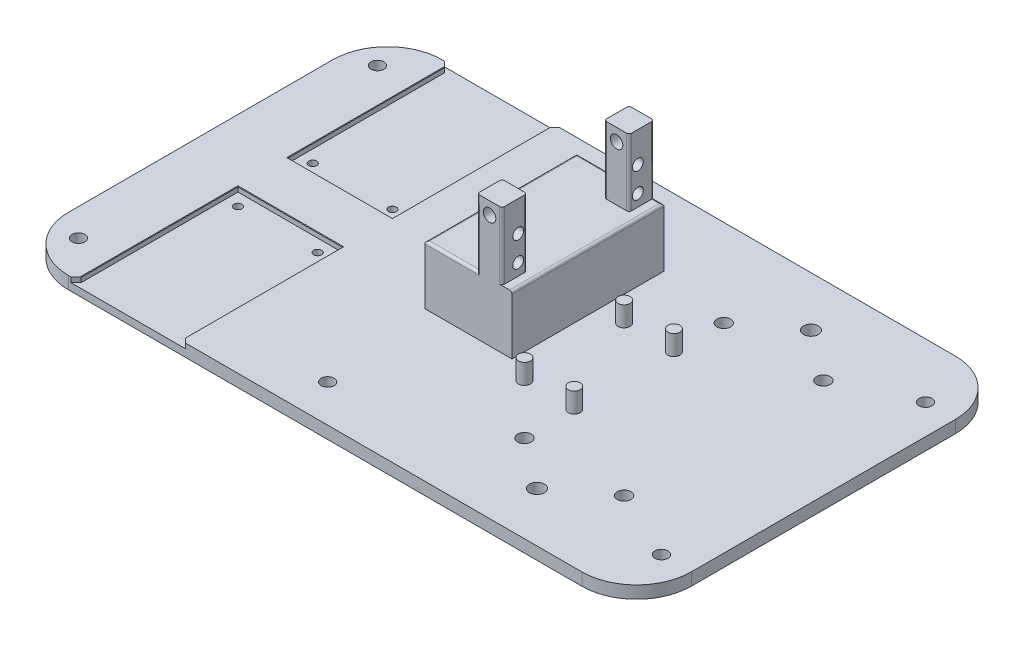
SolidWorks part; units mm, degrees
ref_plane "前视基准面" through (0, 0, 0) normal (0, 0, 1) x (1, 0, 0)
ref_plane "上视基准面" through (0, 0, 0) normal (0, 1, 0) x (1, 0, 0)
ref_plane "右视基准面" through (0, 0, 0) normal (1, 0, 0) x (0, 0, -1)
other "Configuration Table"
sketch "草图1" plane through (0, 0, 0) normal (0, 1, 0) x (1, 0, 0)
  line L0 (103, 75) -> (95, 75)
  line L5 (-125, 53) -> (-125, -53)
  line L6 (-103, -75) -> (55, -75)
  line L7 (125, -53) -> (125, 53)
  line L8 (-1000, 0) -> (49000, 0) construction
  line L9 (55, -75) -> (95, -75)
  line L14 (55, 75) -> (95, 75)
  line L15 (45, -40) -> (85, -40) construction
  line L20 (55, 75) -> (-103, 75)
  line L21 (95, -75) -> (103, -75)
  arc A0 (125, 53) -> (103, 75) centre (103, 53) ccw
  arc A1 (-103, 75) -> (-125, 53) centre (-103, 53) ccw
  arc A2 (-125, -53) -> (-103, -75) centre (-103, -53) ccw
  arc A3 (103, -75) -> (125, -53) centre (103, -53) ccw
  circle A4 centre (-114, 60) radius 2.6
  circle A5 centre (-14, 60) radius 2.6
  circle A6 centre (113, 53) radius 2.6
  circle A7 centre (-114, -60) radius 2.6
  circle A8 centre (-14, -60) radius 2.6
  circle A9 centre (113, -53) radius 2.6
  circle A10 centre (65, -55) radius 3
  circle A11 centre (65, 55) radius 3
  circle A12 centre (45, -40) radius 2.75
  circle A13 centre (85, -40) radius 2.75
  circle A14 centre (85, 40) radius 2.75
  circle A15 centre (45, 40) radius 2.75
  dimension "D3" = 22
  dimension "D4" = 22
  dimension "D5" = 22
  dimension "D6" = 22
  dimension "D9" = 100
  dimension "D10" = 127
  dimension "D11" = 22
  dimension "D12" = 127
  dimension "D13" = 100
  dimension "D14" = 120
  dimension "D15" = 7
  dimension "D16" = 11
  dimension "D17" = 60
  dimension "D18" = 20
  dimension "D19" = 6
  dimension "D20" = 5.5
  dimension "D21" = 5.5
  dimension "D23" = 20
  dimension "D24" = 20
  dimension "D25" = 5.2
  dimension "D1" = 150
  dimension "D2" = 250
  dimension "D7" = 125
  dimension "D8" = 75
  dimension "D22" = 15
extrude "凸台-拉伸1" add sketch "草图1" along normal blind 5
sketch "草图2" plane through (0, 5, 0) normal (0, 1, 0) x (1, 0, 0)
  line L0 (-103, -75) -> (103, -75) construction
  line L1 (-100, -75) -> (-58, -75)
  line L2 (-100, -75) -> (-100, -10)
  line L3 (-100, -10) -> (-58, -10)
  line L4 (-58, -75) -> (-58, -10)
  line L5 (-125, 53) -> (-125, -53) construction
  line L6 (-1000, 0) -> (49000, 0) construction
  line L7 (-58, 75) -> (-58, 10)
  line L8 (-100, 10) -> (-58, 10)
  line L9 (-100, 75) -> (-100, 10)
  line L10 (-100, 75) -> (-58, 75)
  dimension "D1" = 42
  dimension "D2" = 25
  dimension "D3" = 65
extrude "切除-拉伸1" cut sketch "草图2" against normal blind 2
chamfer "倒角1" distance 0.2 angle 45 6 edges at (-58, 5, -42.5) (-79, 5, -10) (-100, 5, -42.5) (-58, 5, 42.5) (-79, 5, 10) (-100, 5, 42.5)
sketch "草图3" plane through (0, 3, 0) normal (0, 1, 0) x (1, 0, 0)
  line L0 (-1000, 0) -> (49000, 0) construction
  line L1 (-100, 10) -> (-58, 10) construction
  line L2 (-58, 10) -> (-58, 75) construction
  line L3 (-100, 75) -> (-100, 10) construction
  circle A0 centre (-95, 15) radius 1.6
  circle A1 centre (-63, 15) radius 1.6
  circle A2 centre (-63, -15) radius 1.6
  circle A3 centre (-95, -15) radius 1.6
  dimension "D1" = 3.2
  dimension "D2" = 3.2
  dimension "D3" = 5
  dimension "D4" = 5
  dimension "D5" = 5
  dimension "D6" = 5
extrude "切除-拉伸2" cut sketch "草图3" against normal blind 3
sketch "草图4" plane through (0, 5, 0) normal (0, 1, 0) x (1, 0, 0)
  line L0 (-1000, 0) -> (49000, 0) construction
  line L1 (0, -1000) -> (0, 49000) construction
  line L2 (103, 75) -> (-57.8, 75) construction
  line L3 (25, -20) -> (45, -20) construction
  line L4 (25, -20) -> (25, 20) construction
  line L5 (25, 20) -> (45, 20) construction
  line L6 (45, -20) -> (45, 20) construction
  line L7 (25, -20) -> (45, 20) construction
  line L8 (25, 20) -> (45, -20) construction
  line L9 (-20, 46) -> (10, 46) construction
  line L10 (-20, 46) -> (-20, -15) construction
  line L11 (-20, -15) -> (10, -15) construction
  line L12 (10, 46) -> (10, -15) construction
  line L13 (-57.8, -75) -> (103, -75) construction
  line L14 (-125, 53) -> (-125, -53) construction
  circle A0 centre (25, 20) radius 2.4
  circle A1 centre (45, 20) radius 2.4
  circle A2 centre (45, -20) radius 2.4
  circle A3 centre (25, -20) radius 2.4
  point P4 (35, 0)
  dimension "D4" = 4.8
  dimension "D1" = 40
  dimension "D2" = 20
  dimension "D3" = 25
  dimension "D7" = 29
  dimension "D8" = 60
  dimension "D9" = 30
  dimension "D10" = 105
  dimension "D5" = 2
  dimension "D6" = 2
chamfer "倒角2" distance 2 4 edges at (-100, 3.9, -75) (-58, 3.9, -75) (-58, 3.9, 75) (-100, 3.9, 75)
extrude "凸台-拉伸2" add sketch "草图4" along normal blind 8
sketch "草图5" plane through (0, 5, 0) normal (0, 1, 0) x (1, 0, 0)
  line L0 (-56, -75) -> (103, -75) construction
  line L1 (-20, 46) -> (15, 46)
  line L2 (-20, 46) -> (-20, -15)
  line L3 (-20, -15) -> (15, -15)
  line L4 (15, 46) -> (15, -15)
  line L5 (103, 75) -> (-56, 75) construction
  line L6 (-125, 53) -> (-125, -53) construction
  dimension "D1" = 60
  dimension "D2" = 29
  dimension "D3" = 105
  dimension "D4" = 35
extrude "凸台-拉伸3" add sketch "草图5" along normal blind 23.5
sketch "草图7" plane through (0, 28.5, 0) normal (0, 1, 0) x (1, 0, 0)
  line L0 (15, -15) -> (15, 46) construction
  line L1 (-20, 46) -> (15, 46)
  line L2 (-20, 46) -> (-20, 36)
  line L3 (-20, 36) -> (15, 36)
  line L4 (15, 46) -> (15, 36)
  line L5 (-1020, 15.5) -> (48980, 15.5) construction
  line L6 (-20, 46) -> (-20, -15) construction
  line L7 (15, -15) -> (15, -5)
  line L8 (-20, -5) -> (15, -5)
  line L9 (-20, -15) -> (-20, -5)
  line L10 (-20, -15) -> (15, -15)
  point P12 (-20, 15.5)
  dimension "D1" = 10
extrude "凸台-拉伸4" add sketch "草图7" along normal blind 30
sketch "草图8" plane through (0, 58.5, 0) normal (0, 1, 0) x (1, 0, 0)
  line L0 (11, 46) -> (11, 36)
  line L1 (-20, 46) -> (-20, -15) construction
  line L2 (1, 46) -> (1, 36)
  line L3 (1, 46) -> (-20, 46)
  line L4 (-20, 46) -> (-20, 36)
  line L5 (-20, 36) -> (15, 36)
  line L6 (15, 36) -> (15, 46)
  line L7 (15, 46) -> (-20, 46)
  line L8 (-20, 46) -> (-20, 36)
  line L9 (-20, 36) -> (1, 36)
  line L10 (15, 36) -> (15, 46)
  line L11 (15, 46) -> (11, 46)
  line L12 (11, 36) -> (15, 36)
  line L13 (-1020, 15.5) -> (48980, 15.5) construction
  line L14 (11, -5) -> (15, -5)
  line L15 (15, -15) -> (11, -15)
  line L16 (15, -5) -> (15, -15)
  line L17 (-20, -5) -> (1, -5)
  line L18 (-20, -15) -> (-20, -5)
  line L19 (1, -15) -> (-20, -15)
  line L20 (1, -15) -> (1, -5)
  line L21 (11, -15) -> (11, -5)
  point P13 (-20, 15.5)
  dimension "D2" = 31
  dimension "D3" = 10
  dimension "D1" = 0
extrude "切除-拉伸3" cut sketch "草图8" against normal up to surface (30 mm away) up to face at (-2.5, 28.5, -15.5)
fillet "圆角1" radius 1 14 edges at (11, 43.5, -46) (11, 43.5, -36) (1, 43.5, -36) (1, 43.5, -46) (-9.5, 28.5, 15) (13, 28.5, 15) (15, 28.5, -15.5) (13, 28.5, -46) (-9.5, 28.5, -46) (-20, 28.5, -15.5) (11, 43.5, 5) (11, 43.5, 15) (1, 43.5, 5) (1, 43.5, 15)
sketch "草图9" plane through (1, 0, 0) normal (-1, 0, 0) x (0, 0, 1)
  line L0 (-1040.8524, 43.3) -> (48959.1476, 43.3) construction
  line L1 (-1040.8524, 33.3) -> (48959.1476, 33.3) construction
  line L2 (-39.5, -955.752) -> (-39.5, 49044.248) construction
  line L3 (8.5, -955.752) -> (8.5, 49044.248) construction
  line L4 (-45, 28.5) -> (14, 28.5) construction
  line L5 (-15.5, -971.5) -> (-15.5, 49028.5) construction
  circle A0 centre (-39.5, 43.3) radius 2.2
  circle A1 centre (-39.5, 33.3) radius 2.2
  circle A2 centre (8.5, 43.3) radius 2.2
  circle A3 centre (8.5, 33.3) radius 2.2
  point P22 (-15.5, 28.5)
  dimension "D1" = 4.4
  dimension "D2" = 48
  dimension "D3" = 10
  dimension "D4" = 4.8
  dimension "D5" = 24
extrude "切除-拉伸4" cut sketch "草图9" against normal through all
sketch "草图10" plane through (0, 0, 15) normal (0, 0, 1) x (1, 0, 0)
  line L0 (6, -941.5) -> (6, 49058.5) construction
  line L1 (2, 58.5) -> (10, 58.5) construction
  line L2 (-19, 28.5) -> (1, 28.5) construction
  line L3 (1, 55.5) -> (11, 55.5)
  line L4 (1, 28.5) -> (1, 58.5) construction
  line L5 (11, 58.5) -> (11, 28.5) construction
  line L6 (11, 55.5) -> (11, 58.5)
  line L7 (11, 58.5) -> (1, 58.5)
  line L8 (1, 58.5) -> (1, 55.5)
  circle A0 centre (6, 50.5) radius 2.5
  point P7 (6, 58.5)
  dimension "D1" = 5
  dimension "D2" = 22
  dimension "D3" = 3
extrude "切除-拉伸5" cut sketch "草图10" against normal through all
